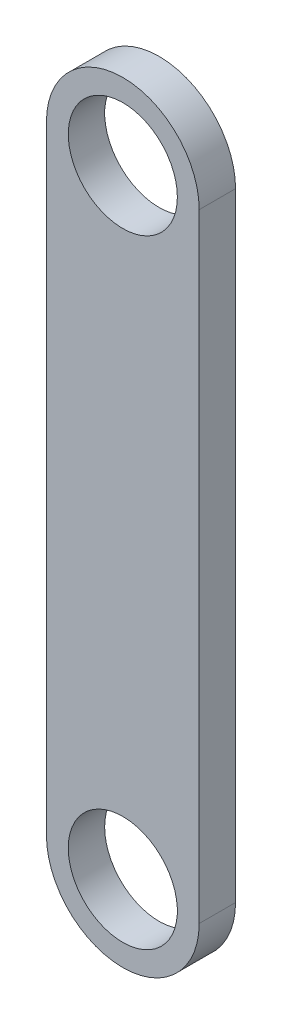
SolidWorks part; units mm, degrees
ref_plane "Front Plane" through (0, 0, 0) normal (0, 0, 1) x (1, 0, 0)
ref_plane "Top Plane" through (0, 0, 0) normal (0, 1, 0) x (1, 0, 0)
ref_plane "Right Plane" through (0, 0, 0) normal (1, 0, 0) x (0, 0, -1)
sketch "Sketch_Swinging Arm" plane through (0, 0, 0) normal (0, 0, 1) x (1, 0, 0)
  line L0 (-10.5, 42.5) -> (-10.5, -42.5)
  line L1 (10.5, 42.5) -> (10.5, -42.5)
  line L2 (10.5, 0) -> (-10.5, 0) construction
  circle A0 centre (0, 42.5) radius 7.5
  arc A1 (10.5, 42.5) -> (-10.5, 42.5) centre (0, 42.5) ccw
  arc A2 (10.5, -42.5) -> (-10.5, -42.5) centre (0, -42.5) cw
  circle A3 centre (0, 42.5) radius 10.5 construction
  circle A4 centre (0, -42.5) radius 7.5
  point P9 (10.5, 0)
  dimension "D1" = 15
  dimension "D3" = 85
  dimension "D2" = 3
extrude "Swinging Arm" add sketch "Sketch_Swinging Arm" against normal blind 5
equation "\"D3@Sketch_Swinging Arm\"=85"
